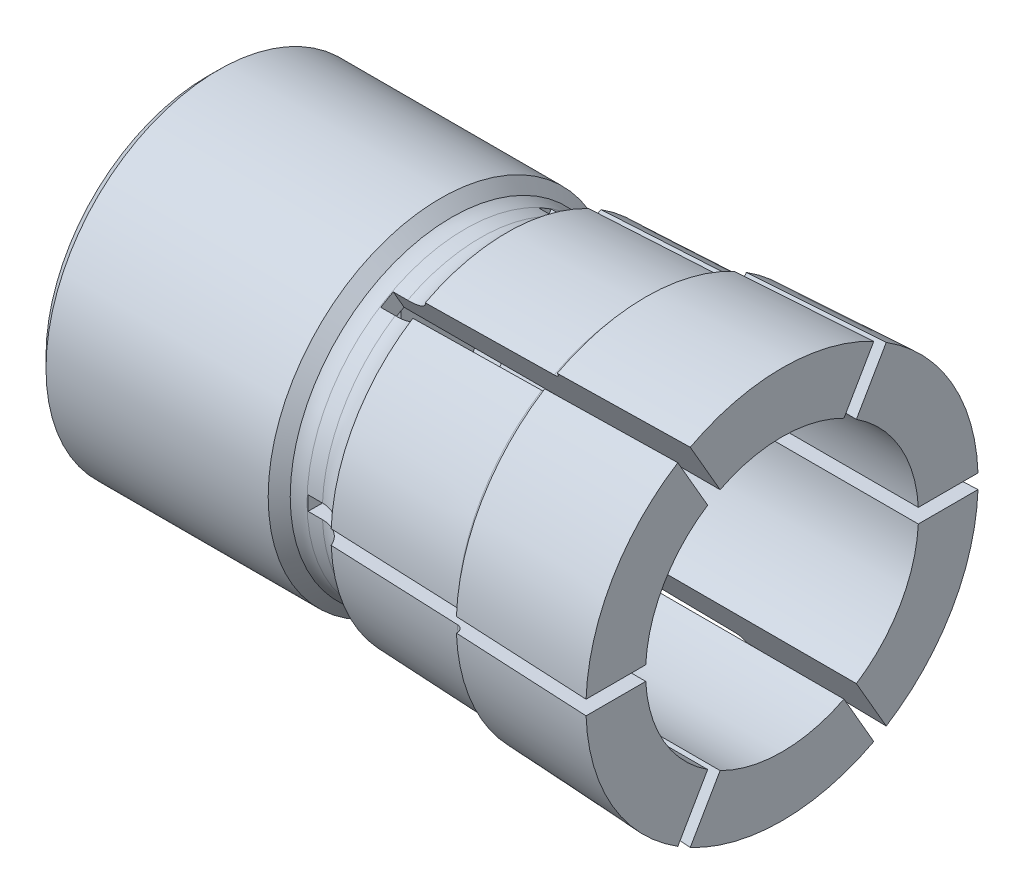
SolidWorks part; units mm, degrees
ref_plane "Front Plane" through (0, 0, 0) normal (0, 0, 1) x (1, 0, 0)
ref_plane "Top Plane" through (0, 0, 0) normal (0, 1, 0) x (1, 0, 0)
ref_plane "Right Plane" through (0, 0, 0) normal (1, 0, 0) x (0, 0, -1)
sketch "Sketch1" plane through (0, 0, 0) normal (0, 0, 1) x (1, 0, 0)
  line L0 (8.054, 0) -> (0, 4.65)
  line L1 (0, 4.65) -> (0, 11.233)
  line L2 (0, 11.233) -> (0.767, 12)
  line L3 (0.767, 12) -> (16.233, 12)
  line L4 (16.233, 12) -> (16.9998, 11.2332)
  line L5 (17.937, 11) -> (19, 11)
  line L6 (20.8515, 12.2437) -> (30.021, 12.6298)
  line L7 (30.5, 13.1294) -> (30.5, 13.175)
  line L8 (30.5, 13.175) -> (40, 13.65)
  line L9 (40, 13.65) -> (40, 0)
  line L10 (40, 0) -> (8.054, 0)
  line L11 (40, 0) -> (8.054, 0) construction
  arc A0 (16.9998, 11.2332) -> (17.937, 11) centre (17.937, 13) ccw
  arc A1 (19, 11) -> (20.8515, 12.2437) centre (19, 13) ccw
  arc A2 (30.021, 12.6298) -> (30.5, 13.1294) centre (30, 13.1294) ccw
revolve "Revolve1" add sketch "Sketch1" angle 360 about L11 reverse direction yes
cosmetic thread "Cosmetic Thread1" parameters "D1"=16.9998, "D2"=22.466
ref_plane "Plane1" through (17.8, 0, 0) normal (1, 0, 0) x (0, 0, -1)
ref_plane "Plane2" through (22.5, 0, 0) normal (1, 0, 0) x (0, 0, -1)
ref_plane "Plane3" through (31, 0, 0) normal (1, 0, 0) x (0, 0, -1)
ref_plane "Plane4" through (33.1, 0, 0) normal (1, 0, 0) x (0, 0, -1)
ref_plane "Plane5" through (41.3, 0, 0) normal (1, 0, 0) x (0, 0, -1)
sketch "Sketch2" plane through (0, 0, 0) normal (1, 0, 0) x (0, 0, -1)
  line L0 (-4, -2.3094) -> (0, -4.6188)
  line L1 (0, -4.6188) -> (4, -2.3094)
  line L2 (4, -2.3094) -> (4, 2.3094)
  line L3 (4, 2.3094) -> (0, 4.6188)
  line L4 (0, 4.6188) -> (-4, 2.3094)
  line L5 (-4, 2.3094) -> (-4, -2.3094)
extrude "Cut-Extrude1" cut sketch "Sketch2" along normal blind 6
sketch "Sketch3" plane through (0, 0, 0) normal (0, 1, 0) x (1, 0, 0)
  line L0 (6, 0) -> (6, 4.75)
  line L1 (6, 4.75) -> (8, 4.75)
  line L2 (8, 4.75) -> (8, 3.5)
  line L3 (8, 3.5) -> (10, 3.5)
  line L4 (10, 3.5) -> (10, 9.7)
  line L5 (10, 9.7) -> (12, 9.7)
  line L6 (12, 9.7) -> (12, 9.5)
  line L7 (12, 9.5) -> (42, 9.5)
  line L8 (42, 9.5) -> (42, 0)
  line L9 (42, 0) -> (6, 0)
  line L10 (42, 0) -> (6, 0) construction
revolve "Cut-Revolve1" cut sketch "Sketch3" angle 360 about L10 reverse direction yes
ref_plane "Plane6" through (18, 0, 0) normal (1, 0, 0) x (0, 0, -1)
sketch "Sketch4" plane through (18, 0, 0) normal (1, 0, 0) x (0, 0, -1)
  line L0 (-18.65, 0.5) -> (-18.65, -0.5)
  line L1 (-18.65, -0.5) -> (-0.866, -0.5)
  line L2 (-0.866, -0.5) -> (-9.758, -15.9014)
  line L3 (-9.758, -15.9014) -> (-8.892, -16.4014)
  line L4 (-8.892, -16.4014) -> (0, -1)
  line L5 (0, -1) -> (8.892, -16.4014)
  line L6 (8.892, -16.4014) -> (9.758, -15.9014)
  line L7 (9.758, -15.9014) -> (0.866, -0.5)
  line L8 (0.866, -0.5) -> (18.65, -0.5)
  line L9 (18.65, -0.5) -> (18.65, 0.5)
  line L10 (18.65, 0.5) -> (0.866, 0.5)
  line L11 (0.866, 0.5) -> (9.758, 15.9014)
  line L12 (9.758, 15.9014) -> (8.892, 16.4014)
  line L13 (8.892, 16.4014) -> (0, 1)
  line L14 (0, 1) -> (-8.892, 16.4014)
  line L15 (-8.892, 16.4014) -> (-9.758, 15.9014)
  line L16 (-9.758, 15.9014) -> (-0.866, 0.5)
  line L17 (-0.866, 0.5) -> (-18.65, 0.5)
extrude "Cut-Extrude2" cut sketch "Sketch4" along normal blind 40
ref_plane "Plane7" through (40, 0, 0) normal (1, 0, 0) x (0, 0, -1)
ref_plane "ANBAU XY" through (40, 0, 0) normal (1, 0, 0) x (0, 0, -1)
ref_plane "ANBAU XZ" through (0, 0, 0) normal (0, -1, 0) x (-1, 0, 0)
ref_plane "ANBAU YZ" through (0, 0, 0) normal (0, 0, -1) x (-1, 0, 0)
ref_axis "ANBAU X" through (40, 0, 80.9) along (0, 0, -1)
ref_axis "ANBAU Y" through (40, -50, 0) along (0, 1, 0)
ref_axis "ANBAU Z" through (80.9, 0, 0) along (-1, 0, 0)
sketch3d "ANBAU"
  point P0 (40, 0, 0)
other "Freeze***"
